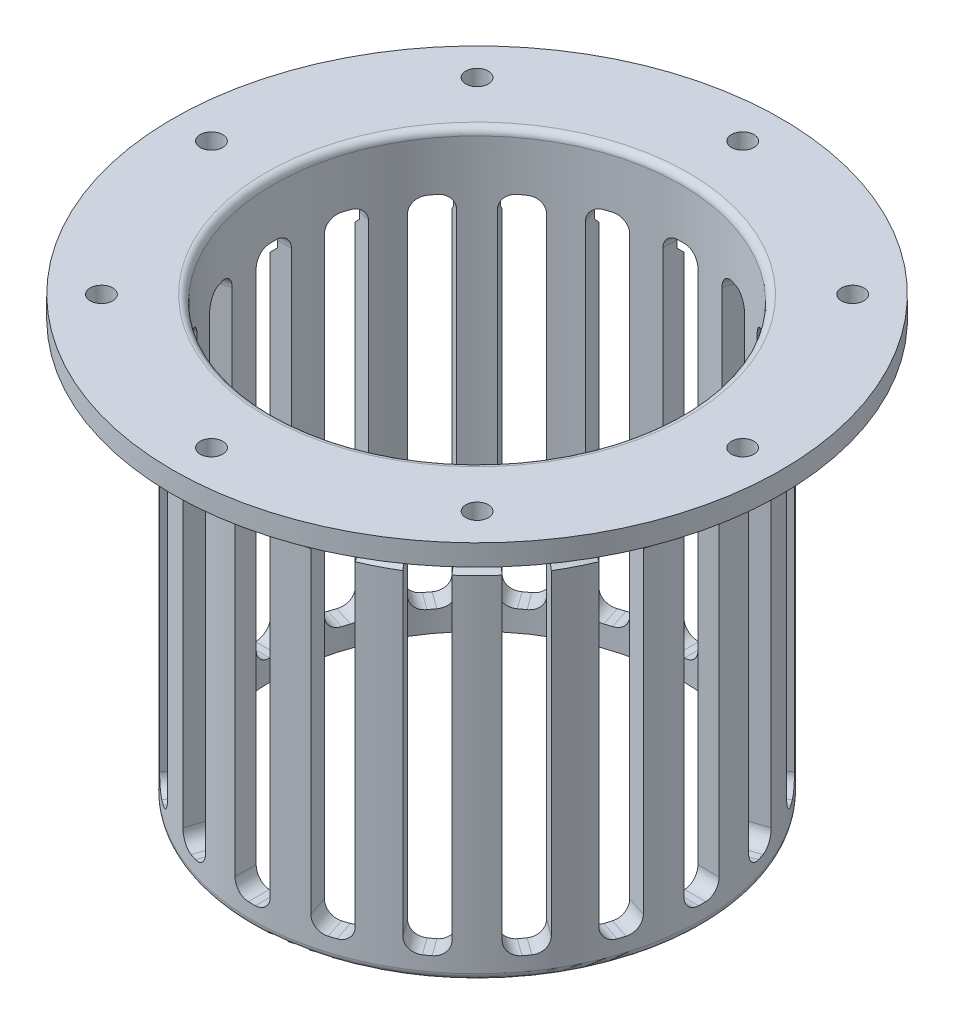
SolidWorks part; units mm, degrees
ref_plane "Front Plane" through (0, 0, 0) normal (0, 0, 1) x (1, 0, 0)
ref_plane "Top Plane" through (0, 0, 0) normal (0, 1, 0) x (1, 0, 0)
ref_plane "Right Plane" through (0, 0, 0) normal (1, 0, 0) x (0, 0, -1)
sketch "Sketch1" plane through (0, 0, 0) normal (0, 1, 0) x (1, 0, 0)
  circle A0 centre (0, 0) radius 32
  circle A1 centre (0, 0) radius 43.25
  circle A2 centre (0, 0) radius 37.75 construction
  circle A3 centre (0, 37.75) radius 1.6
  circle A4 centre (26.6933, 26.6933) radius 1.6
  circle A5 centre (37.75, 0) radius 1.6
  circle A6 centre (26.6933, -26.6933) radius 1.6
  circle A7 centre (0, -37.75) radius 1.6
  circle A8 centre (-26.6933, -26.6933) radius 1.6
  circle A9 centre (-37.75, 0) radius 1.6
  circle A10 centre (-26.6933, 26.6933) radius 1.6
  circle A11 centre (0, 0) radius 45.25 construction
  point P23 (0, 0)
  dimension "D1" = 64
  dimension "D2" = 86.5
  dimension "D3" = 3.2
  dimension "D5" = 90.5
  dimension "D6" = 7.5
  dimension "D4" = 8
extrude "Boss-Extrude1" add sketch "Sketch1" along normal blind 3
sketch "Sketch2" plane through (0, 0, 0) normal (0, -1, 0) x (1, 0, 0)
  circle A0 centre (0, 0) radius 32
  circle A1 centre (0, 0) radius 32 construction
  circle A2 centre (0, 0) radius 29
  dimension "D1" = 3
extrude "Boss-Extrude2" add sketch "Sketch2" along normal blind 5 and the other way up to surface (3 mm away) other way up to face at (-37.75, 3, 1.6)
sketch "Sketch3" plane through (0, -5, 0) normal (0, -1, 0) x (1, 0, 0)
  circle A0 centre (0, 0) radius 29
  circle A1 centre (0, 0) radius 31
  circle A2 centre (0, 0) radius 29 construction
  dimension "D1" = 2
extrude "Boss-Extrude3" add sketch "Sketch3" along normal blind 4
sketch "Sketch4" plane through (0, -9, 0) normal (0, -1, 0) x (1, 0, 0)
  circle A0 centre (0, 0) radius 29
  circle A1 centre (0, 0) radius 32
  circle A2 centre (0, 0) radius 32 construction
  circle A3 centre (0, 0) radius 29 construction
extrude "Boss-Extrude4" add sketch "Sketch4" along normal blind 50
sketch "Sketch5" plane through (0, 0, 0) normal (1, 0, 0) x (0, 0, -1)
  line L0 (-31, -5) -> (31, -5) construction
  line L1 (-2.5, -5) -> (2.5, -5)
  line L2 (-2.5, -5) -> (-2.5, -56)
  line L3 (-2.5, -56) -> (2.5, -56)
  line L4 (2.5, -5) -> (2.5, -56)
  line L5 (0, 0) -> (0, -59) construction
  line L6 (-32, -59) -> (32, -59) construction
  point P11 (0, -56)
  dimension "D1" = 5
  dimension "D2" = 3
extrude "Cut-Extrude1" cut sketch "Sketch5" against normal blind 50
fillet "Fillet1" radius 2 4 edges at (-30.3971, -56, -2.5) (-30.3971, -56, 2.5) (-29.8955, -5, -2.5) (-29.8955, -5, 2.5)
pattern_circular "CirPattern1" count 20 over 360 about axis through (0, -59, 0) along (0, 1, 0) of "Fillet1", "Cut-Extrude1"
fillet "Fillet2" radius 1 2 edges at (0, 0, 32) (0, 3, 29)
chamfer "Chamfer1" distance 1 angle 45 20 edges at (27.6212, -9, -14.0737) (21.9203, -9, -21.9203) (14.0737, -9, -27.6212) (4.8495, -9, -30.6183) (-4.8495, -9, -30.6183) (30.6183, -9, -4.8495) (30.6183, -9, 4.8495) (27.6212, -9, 14.0737) (21.9203, -9, 21.9203) (14.0737, -9, 27.6212) (4.8495, -9, 30.6183) (-4.8495, -9, 30.6183) (-14.0737, -9, 27.6212) (-21.9203, -9, 21.9203) (-27.6212, -9, 14.0737) (-30.6183, -9, 4.8495) (-30.6183, -9, -4.8495) (-27.6212, -9, -14.0737) (-21.9203, -9, -21.9203) (-14.0737, -9, -27.6212)
fillet "Fillet3" radius 1 1 edges at (0, -59, -32)
